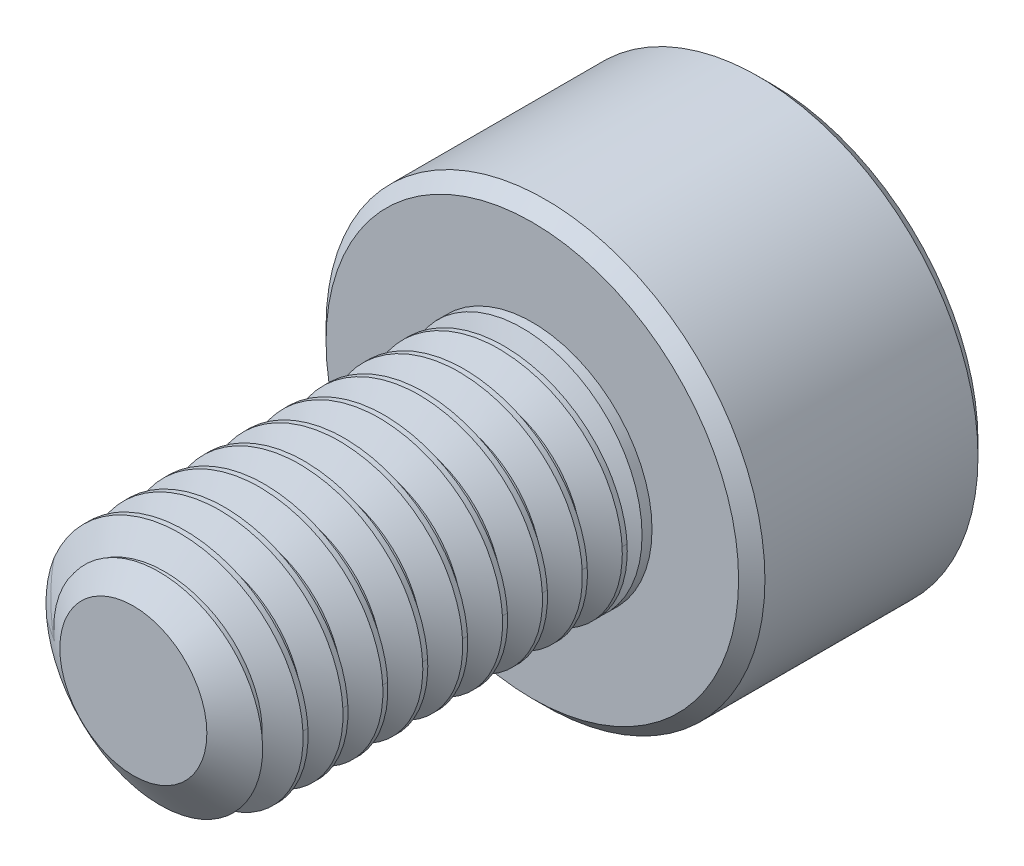
SolidWorks part; units mm, degrees
ref_plane "Front Plane" through (0, 0, 0) normal (0, 0, 1) x (1, 0, 0)
ref_plane "Top Plane" through (0, 0, 0) normal (0, 1, 0) x (1, 0, 0)
ref_plane "Right Plane" through (0, 0, 0) normal (1, 0, 0) x (0, 0, -1)
sketch "Sketch1" plane through (0, 0, 0) normal (0, 0, 1) x (1, 0, 0)
  circle A0 centre (0, 0) radius 1.5
  dimension "OD" = 3
extrude "Extrude1" add sketch "Sketch1" against normal blind 5
sketch "Sketch2" plane through (0, 0, 0) normal (0, 0, 1) x (1, 0, 0)
  circle A0 centre (0, 0) radius 1.5 construction
  circle A1 centre (0, 0) radius 1.5
curve "Helix/Spiral1" pitch 0.5 height 5.5 radius 1.5 centre (0, 0, 0) axis (0, 0, -1) start towards (0, 1, 0) parameters "pitch"=0.5
sketch "Sketch3" plane through (0, 0, 0) normal (1, 0, 0) x (0, 0, -1)
  line L0 (-0.4375, 1.5) -> (-0.25, 1.1752)
  line L1 (-0.25, 1.1752) -> (-0.1875, 1.1752)
  line L2 (-0.1875, 1.1752) -> (0, 1.5)
  line L3 (-0.4375, 1.5) -> (0, 1.5)
  line L4 (-0.2187, 1.5) -> (-0.2187, 1.1752) construction
  line L5 (-0.3437, 1.3376) -> (-0.0937, 1.3376) construction
  line L6 (0, 1.5) -> (0, -1.5) construction
  line L7 (0, -1.5) -> (5, -1.5) construction
  point P11 (2.25, -1.5)
  dimension "D1" = 0.0625
  dimension "D2" = 0.25
  dimension "D3" = 60
  dimension "D4" = 2.25
sweep "Cut-Sweep1" cut profiles "Sketch3" path "Helix/Spiral1" align with end faces yes
sketch "Sketch4" plane through (0, 0, 0) normal (1, 0, 0) x (0, 0, -1)
  line L0 (0.4053, 1.5) -> (0, 0.9212)
  line L1 (0, 0.9212) -> (0, 1.5)
  line L2 (0.4053, 1.5) -> (0, 1.5)
  line L3 (-0.4375, 1.5) -> (0, 1.5) construction
  line L4 (0, 0) -> (7.0209, 0) construction
  dimension "D1" = 55
  dimension "D2" = 0.254
revolve "Cut-Revolve1" cut sketch "Sketch4" angle 360 about L4
sketch "Sketch5" plane through (0, 0, 0) normal (1, 0, 0) x (0, 0, -1)
  line L0 (5, -1.1822) -> (5, 1.0703) construction
  line L1 (5, 1.5) -> (0.1203, 1.5)
  line L2 (5, 1.5) -> (5, 0)
  line L3 (5, 0) -> (0.0001, 0)
  line L4 (0.0001, 1.1698) -> (0.0001, 0)
  line L5 (0.1203, 1.5) -> (0.0001, 1.1698)
  line L6 (0, 0) -> (9.9695, 0) construction
  point P3 (0.0001, 1.5)
  point P10 (0.0001, 1.5)
  dimension "D1" = 0.3302
  dimension "Thread min" = 0.0001
  dimension "D3" = 20
revolve "partially thread" [suppressed] add sketch "Sketch5" angle 360 about L6
sketch "Sketch6" plane through (0, 0, -5) normal (0, 0, -1) x (-1, 0, 0)
  circle A0 centre (0, 0) radius 2.75
  dimension "head dia" = 5.5
extrude "Extrude2" add sketch "Sketch6" along normal blind 3
sketch "Sketch7" plane through (0, 0, -8) normal (0, 0, -1) x (-1, 0, 0)
  line L1 (0, 1.4434) -> (-1.25, 0.7217)
  line L2 (-1.25, 0.7217) -> (-1.25, -0.7217)
  line L3 (-1.25, -0.7217) -> (0, -1.4434)
  line L4 (0, -1.4434) -> (1.25, -0.7217)
  line L5 (1.25, -0.7217) -> (1.25, 0.7217)
  line L6 (1.25, 0.7217) -> (0, 1.4434)
  circle A0 centre (0, 0) radius 1.25 construction
  dimension "hex dia" = 2.5
extrude "Cut-Extrude1" cut sketch "Sketch7" against normal blind 1.875
sketch "Sketch8" plane through (0, 0, -8) normal (0, 0, -1) x (-1, 0, 0)
  circle A0 centre (0, 0) radius 1.4434
extrude "Cut-Extrude2" cut sketch "Sketch8" against normal through all draft 45
chamfer "Chamfer1" distance 0.165 angle 45 2 edges at (-2.75, 0, -8) (-2.75, 0, -5)
sketch "Sketch9" plane through (0, 0, 0) normal (1, 0, 0) x (0, 0, -1)
  line L0 (0, 1.5) -> (0, -1.5) construction
  line L1 (2.75, 1.5) -> (2.75, -1.5) construction
  dimension "D1" = 2.75
sketch "Sketch10" plane through (0, 0, 0) normal (1, 0, 0) x (0, 0, -1)
  line L0 (5, 1.5) -> (5, 0)
  line L1 (5, 1.5) -> (4.875, 1.5)
  line L2 (4.875, 1.5) -> (4.2537, 0)
  line L3 (5, 0) -> (4.2537, 0)
  line L4 (5, 2.585) -> (5, -2.585) construction
  dimension "D1" = 22.5
  dimension "D2" = 0.125
revolve "Revolve1" add sketch "Sketch10" angle 360 about L3
equation "\"D3@Helix/Spiral1\" = \"screw length@Extrude1\"+\"pitch@Helix/Spiral1\""
equation "\"D1@Sketch3\" = \"pitch@Helix/Spiral1\"*.125"
equation "\"D2@Sketch3\" = \"pitch@Helix/Spiral1\"*.5"
equation "\"D1@Cut-Extrude1\" = \"hex dia@Sketch7\"*.75"
equation "\"D1@Chamfer1\" = \"head dia@Sketch6\"*.03"
equation "\"D1@Sketch9\" = \"pitch@Helix/Spiral1\"*5.5"
equation "\"D2@Sketch10\" = \"pitch@Helix/Spiral1\"*.25"
equation "\"D4@Sketch3\" = \"pitch@Helix/Spiral1\"*4.50"
